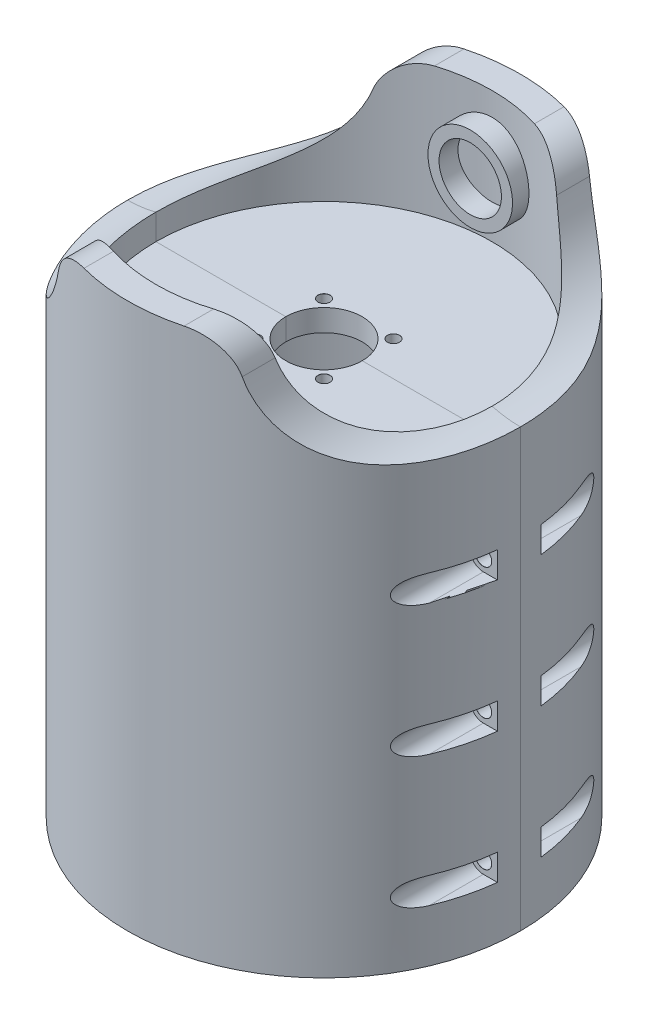
SolidWorks part; units mm, degrees
material "ABS"
ref_plane "Front Plane" through (0, 0, 0) normal (0, 0, 1) x (1, 0, 0)
ref_plane "Top Plane" through (0, 0, 0) normal (0, 1, 0) x (1, 0, 0)
ref_plane "Right Plane" through (0, 0, 0) normal (1, 0, 0) x (0, 0, -1)
sketch "Sketch7" plane through (0, 0, 0) normal (0, 1, 0) x (1, 0, 0)
  circle A0 centre (0, 0) radius 90
  point P0 (0, 0)
  dimension "D1" = 180
extrude "Boss-Extrude3" add sketch "Sketch7" along normal blind 250
sketch "Sketch8" plane through (0, 0, 0) normal (0, 0, 1) x (1, 0, 0)
  line L0 (-83, 210) -> (-83, 90) construction
  line L1 (83, 204) -> (83, 156) construction
  line L2 (90, 250) -> (-90, 250) construction
  line L3 (-90, 250) -> (-90, 0) construction
  line L4 (90, 0) -> (90, 250) construction
  line L5 (-83, 210) -> (-90, 210) construction
  line L6 (83, 210) -> (90, 210) construction
  line L7 (-83, 216) -> (-98, 216)
  line L8 (-98, 216) -> (-98, 204)
  line L9 (-98, 204) -> (-83, 204)
  line L10 (-83, 156) -> (-98, 156)
  line L11 (-98, 156) -> (-98, 144)
  line L12 (-98, 144) -> (-83, 144)
  line L13 (-83, 96) -> (-98, 96)
  line L14 (-98, 96) -> (-98, 84)
  line L15 (-98, 84) -> (-83, 84)
  line L17 (83, 216) -> (105.4044, 174.6914)
  line L18 (83, 204) -> (107.5565, 163.9943)
  line L19 (105.4044, 174.6914) -> (107.5565, 163.9943)
  line L21 (83, 156) -> (116.9139, 117.4845)
  line L22 (83, 144) -> (119.2158, 106.0432)
  line L23 (116.9139, 117.4845) -> (119.2158, 106.0432)
  line L25 (83, 96) -> (128.4235, 60.2777)
  line L26 (83, 84) -> (130.7254, 48.8363)
  line L27 (128.4235, 60.2777) -> (130.7254, 48.8363)
  line L28 (83, 144) -> (83, 96) construction
  arc A0 (-83, 204) -> (-83, 216) centre (-83, 210) ccw
  arc A1 (-83, 144) -> (-83, 156) centre (-83, 150) ccw
  arc A2 (-83, 84) -> (-83, 96) centre (-83, 90) ccw
  arc A3 (83, 216) -> (83, 204) centre (83, 210) ccw
  arc A4 (83, 156) -> (83, 144) centre (83, 150) ccw
  arc A5 (83, 96) -> (83, 84) centre (83, 90) ccw
  dimension "D4" = 12
  dimension "D1" = 40
  dimension "D2" = 7
  dimension "D3" = 15
  dimension "D5" = 40
  dimension "D6" = 60
  dimension "D7" = 60
  dimension "D8" = 60
  dimension "D9" = 15
shell "Shell3" thickness 13 removed face at (0, 250, 90) removed face at (0, 0, 90)
ref_plane "Plane1" through (0, 0, 77) normal (0, 0, -1) x (-1, 0, 0)
sketch "Sketch9" plane through (0, 0, 77) normal (0, 0, -1) x (-1, 0, 0)
  line L0 (77, 250) -> (-77, 250) construction
  circle A0 centre (0, 220) radius 19.3675
  circle A1 centre (0, 220) radius 14.2875
  dimension "D1" = 28.575
  dimension "D2" = 5.08
  dimension "D3" = 30
extrude "Boss-Extrude4" add sketch "Sketch9" along normal blind 10
mirror "Mirror1" about plane through (0, 0, 0) normal (0, 0, 1) of "Boss-Extrude4"
ref_plane "Plane2" through (0, 0, 10) normal (0, 0, 1) x (1, 0, 0)
sketch "Sketch11" plane through (0, 0, 10) normal (0, 0, 1) x (1, 0, 0)
  line L0 (-83, 150) -> (-83, 90) construction
  line L1 (-83, 90) -> (-83, 30) construction
  line L2 (-83, 36) -> (-98, 36)
  line L3 (-98, 96) -> (-98, 84)
  line L4 (-98, 84) -> (-83, 84)
  line L5 (-83, 96) -> (-98, 96)
  line L6 (-98, 96) -> (-98, 84)
  line L7 (-98, 84) -> (-83, 84)
  line L8 (-83, 96) -> (-98, 96)
  line L9 (-98, 156) -> (-98, 144)
  line L10 (-98, 144) -> (-83, 144)
  line L11 (-83, 156) -> (-98, 156)
  line L12 (-98, 156) -> (-98, 144)
  line L13 (-98, 144) -> (-83, 144)
  line L14 (-83, 156) -> (-98, 156)
  line L15 (-83, 216) -> (-98, 216)
  line L16 (-98, 216) -> (-98, 204)
  line L17 (-98, 204) -> (-83, 204)
  line L18 (-83, 216) -> (-98, 216)
  line L19 (-98, 216) -> (-98, 204)
  line L20 (-98, 204) -> (-83, 204)
  line L21 (128.4235, 60.2777) -> (83, 96)
  line L22 (130.7254, 48.8363) -> (128.4235, 60.2777)
  line L23 (83, 84) -> (130.7254, 48.8363)
  line L24 (115.4479, 96) -> (83, 96)
  line L25 (115.4479, 84) -> (115.4479, 96)
  line L26 (83, 84) -> (115.4479, 84)
  line L27 (116.9139, 117.4845) -> (83, 156)
  line L28 (119.2158, 106.0432) -> (116.9139, 117.4845)
  line L29 (83, 144) -> (119.2158, 106.0432)
  line L30 (113.0356, 156) -> (83, 156)
  line L31 (113.0356, 144) -> (113.0356, 156)
  line L32 (83, 144) -> (113.0356, 144)
  line L33 (105.4044, 174.6914) -> (83, 216)
  line L34 (83, 204) -> (107.5565, 163.9943)
  line L35 (107.5565, 163.9943) -> (105.4044, 174.6914)
  line L36 (119.1042, 216) -> (83, 216)
  line L37 (83, 204) -> (119.1042, 204)
  line L38 (119.1042, 204) -> (119.1042, 216)
  line L39 (-98, 36) -> (-98, 24)
  line L40 (-98, 24) -> (-83, 24)
  line L41 (0, 0) -> (0, 125.8231) construction
  line L42 (83, 90) -> (83, 30) construction
  line L43 (98, 24) -> (83, 24)
  line L44 (98, 36) -> (98, 24)
  line L45 (83, 36) -> (98, 36)
  arc A0 (-83, 24) -> (-83, 36) centre (-83, 30) ccw
  arc A1 (-83, 84) -> (-83, 96) centre (-83, 90) ccw
  arc A2 (-83, 84) -> (-83, 96) centre (-83, 90) ccw
  arc A3 (-83, 144) -> (-83, 156) centre (-83, 150) ccw
  arc A4 (-83, 144) -> (-83, 156) centre (-83, 150) ccw
  arc A5 (-83, 204) -> (-83, 216) centre (-83, 210) ccw
  arc A6 (-83, 204) -> (-83, 216) centre (-83, 210) ccw
  arc A7 (83, 96) -> (83, 84) centre (83, 90) ccw
  arc A8 (83, 96) -> (83, 84) centre (83, 90) ccw
  arc A9 (83, 156) -> (83, 144) centre (83, 150) ccw
  arc A10 (83, 156) -> (83, 144) centre (83, 150) ccw
  arc A11 (83, 216) -> (83, 204) centre (83, 210) ccw
  arc A12 (83, 216) -> (83, 204) centre (83, 210) ccw
  arc A13 (83, 24) -> (83, 36) centre (83, 30) cw
  dimension "D1" = 0
  dimension "D2" = 0
  dimension "D3" = 0
  dimension "D4" = 0
  dimension "D5" = 0
  dimension "D6" = 0
extrude "Cut-Extrude3" cut sketch "Sketch11" along normal through all
mirror "Mirror2" about plane through (0, 0, 0) normal (0, 0, 1) of "Cut-Extrude3"
sketch "Sketch12" plane through (0, 0, 0) normal (0, 1, 0) x (1, 0, 0)
  circle A0 centre (0, 0) radius 90
  circle A1 centre (0, 0) radius 90 construction
extrude "Boss-Extrude5" add sketch "Sketch12" along normal blind 10
ref_plane "Plane3" through (0, 180, 0) normal (0, 1, 0) x (1, 0, 0)
sketch "Sketch14" plane through (0, 180, 0) normal (0, 1, 0) x (1, 0, 0)
  circle A0 centre (0, 0) radius 77
  circle A1 centre (0, 0) radius 77 construction
extrude "Boss-Extrude6" add sketch "Sketch14" along normal blind 10
sketch "Sketch15" plane through (0, 190, 0) normal (0, 1, 0) x (1, 0, 0)
  line L0 (0, 22.5) -> (0, 0) construction
  line L1 (0, 0) -> (15.9099, 15.9099) construction
  circle A0 centre (0, 0) radius 22.5 construction
  circle A1 centre (0, 0) radius 17.5
  dimension "D1" = 45
  dimension "D2" = 45
  dimension "D3" = 35
extrude "Cut-Extrude4" cut sketch "Sketch15" against normal blind 10
hole_wizard "M5 Clearance Hole1" positions "3DSketch1" profile "Sketch17" hole size "M5" standard "ANSI Metric"
sketch3d "3DSketch1"
  point P0 (15.9099, 190, -15.9099)
sketch "Sketch17" plane through (15.9099, 190, -15.9099) normal (1, 0, 0) x (0, 0, 1)
  line L0 (0, 0) -> (0, 11.6524)
  line L1 (0, 11.6524) -> (2.75, 10)
  line L2 (2.75, 10) -> (2.75, 0.025)
  line L3 (2.75, 0.025) -> (2.775, 0)
  line L5 (2.775, 0) -> (0, 0)
  line L6 (-2.75, 0.025) -> (-2.775, 0) construction
  line L10 (0, 11.6524) -> (-2.75, 10) construction
  line L11 (0, -6.35) -> (0, 107.95) construction
  dimension "Hole Dia." = 5.5
  dimension "Hole Depth" = 10
  dimension "Near C'Sink Dia." = 5.55
  dimension "Near C'Sink Angle" = 90
  dimension "Drill Angle" = 118
pattern_circular "CirPattern1" count 4 over 360 about axis through (0, 10, 0) along (0, 1, 0) of "M5 Clearance Hole1"
sketch "Sketch18" plane through (0, 0, 0) normal (0, 0, 1) x (1, 0, 0)
  line L0 (90, 250) -> (-90, 250) construction
  line L1 (-90, 250) -> (-90, 0) construction
  line L2 (-40, 250) -> (-40, 270)
  line L3 (-40, 270) -> (-110, 270)
  line L4 (-110, 270) -> (-110, 200)
  line L5 (-110, 200) -> (-90, 200)
  line L6 (0, 250) -> (0, 180) construction
  line L7 (77, 250) -> (-77, 250) construction
  line L8 (8.4936, 180) -> (-8.4936, 180) construction
  line L9 (110, 200) -> (90, 200)
  line L10 (110, 270) -> (110, 200)
  line L11 (40, 270) -> (110, 270)
  line L12 (40, 250) -> (40, 270)
  arc A0 (-40, 250) -> (-90, 200) centre (-90, 250) cw
  arc A1 (40, 250) -> (90, 200) centre (90, 250) ccw
  dimension "D1" = 50
  dimension "D2" = 20
  dimension "D3" = 20
extrude "Cut-Extrude5" cut sketch "Sketch18" against normal through all both and the other way through all
fillet "Fillet1" radius 20 4 edges at (40, 250, -73.2089) (40, 250, 73.2089) (-40, 250, 73.2089) (-40, 250, -73.2089)
sketch "Sketch19" plane through (0, 0, 0) normal (0, -1, 0) x (1, 0, 0)
  circle A0 centre (0, 0) radius 17.5
  dimension "D1" = 35
extrude "Cut-Extrude6" cut sketch "Sketch19" against normal blind 47
hole_wizard "M7 Clearance Hole1" positions "Sketch20" profile "Sketch21" hole size "M7" standard "ANSI Metric" end condition through all
sketch "Sketch20" plane through (0, 0, 10) normal (0, 0, 1) x (1, 0, 0)
  point P0 (-83, 150)
  point P5 (-83, 30)
  point P8 (83, 30)
  point P11 (83, 90)
  point P14 (83, 150)
  point P19 (-83, 90)
sketch "Sketch21" plane through (-83, 150, 10) normal (1, 0, 0) x (0, -1, 0)
  line L0 (0, 0) -> (0, 100)
  line L1 (0, 100) -> (3.8, 100)
  line L2 (3.8, 100) -> (3.8, 0.025)
  line L3 (3.8, 0.025) -> (3.825, 0)
  line L5 (3.825, 0) -> (0, 0)
  line L6 (-3.8, 0.025) -> (-3.825, 0) construction
  line L11 (0, -6.35) -> (0, 107.95) construction
  dimension "Thru Hole Dia." = 7.6
  dimension "Thru Hole Depth" = 100
  dimension "Near C'Sink Dia." = 7.65
  dimension "Near C'Sink Angle" = 90
split "Split1" trim tools "Front Plane" bodies to split 126 resulting bodies 127 128
